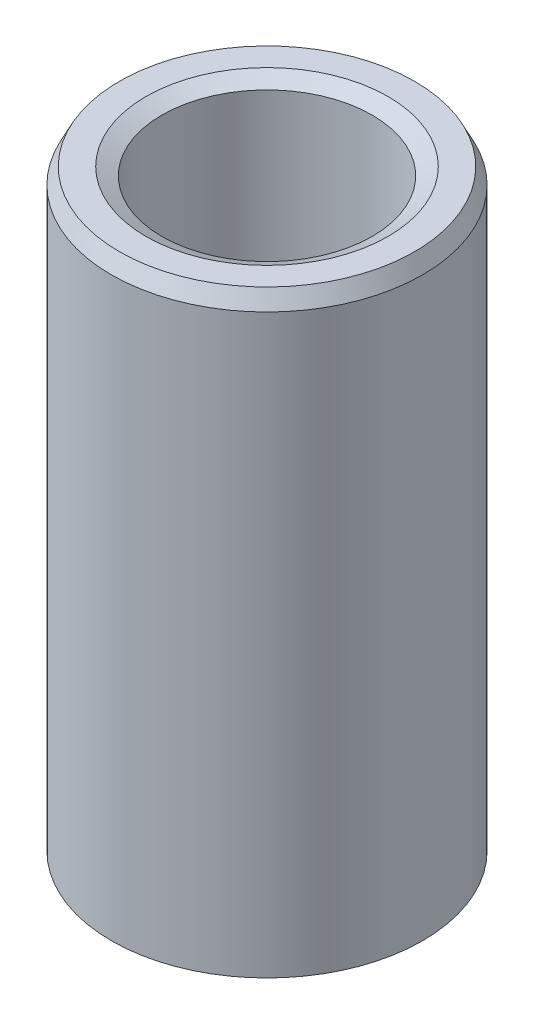
SolidWorks part; units mm, degrees
ref_plane "Front Plane" through (0, 0, 0) normal (0, 0, 1) x (1, 0, 0)
ref_plane "Top Plane" through (0, 0, 0) normal (0, 1, 0) x (1, 0, 0)
ref_plane "Right Plane" through (0, 0, 0) normal (1, 0, 0) x (0, 0, -1)
sketch "Sketch1" plane through (0, 0, 0) normal (0, 1, 0) x (1, 0, 0)
  circle A0 centre (0, 0) radius 15
  dimension "SLEEVE_OD" = 30
extrude "Boss-Extrude1" add sketch "Sketch1" along normal blind 57.9001
sketch "Sketch2" plane through (0, 0, 0) normal (0, 1, 0) x (1, 0, 0)
  circle A0 centre (0, 0) radius 10.135
  dimension "BORE_D" = 20.2699
extrude "Cut-Extrude1" cut sketch "Sketch2" along normal through all
chamfer "Chamfer1" distance 1.5414 angle 26.663 4 edges at (0, 57.9001, 10.135) (0, 0, 10.135) (0, 0, 15) (0, 57.9001, 15) first distance on face at (0, 57.9001, 10.135) first distance on face at (0, 0, 10.135) first distance on face at (0, 57.9001, 15)
